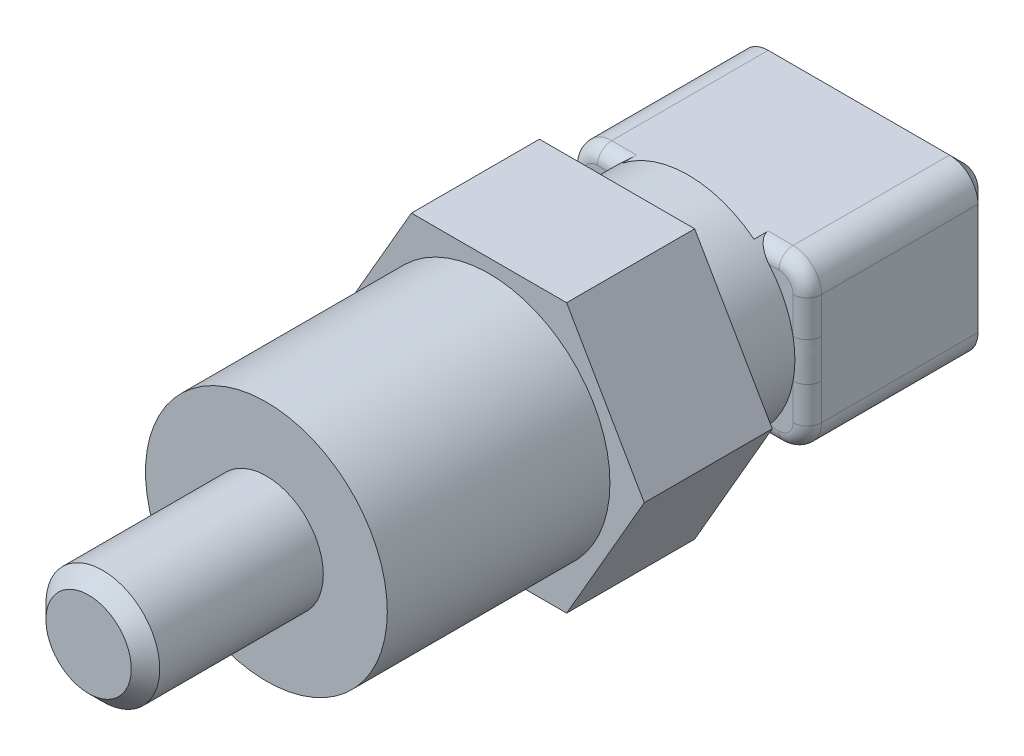
SolidWorks part; units mm, degrees
ref_plane "Front Plane" through (0, 0, 0) normal (0, 0, 1) x (1, 0, 0)
ref_plane "Top Plane" through (0, 0, 0) normal (0, 1, 0) x (1, 0, 0)
ref_plane "Right Plane" through (0, 0, 0) normal (1, 0, 0) x (0, 0, -1)
sketch "Sketch1" plane through (0, 0, 0) normal (0, 0, 1) x (1, 0, 0)
  line L0 (0, 23.3833) -> (0, -23.3833) construction
  line L1 (-5.456, 9.45) -> (-10.9119, 0)
  line L2 (-10.9119, 0) -> (-5.456, -9.45)
  line L3 (-5.456, -9.45) -> (5.456, -9.45)
  line L4 (5.456, -9.45) -> (10.9119, 0)
  line L5 (10.9119, 0) -> (5.456, 9.45)
  line L6 (5.456, 9.45) -> (-5.456, 9.45)
  circle A0 centre (0, 0) radius 9.45 construction
  dimension "D1" = 18.9
extrude "Extrude1" add sketch "Sketch1" along normal blind 9
sketch "Sketch2" plane through (0, 0, 9) normal (0, 0, 1) x (1, 0, 0)
  circle A0 centre (0, 0) radius 4.75
  dimension "D1" = 9.5
extrude "Extrude2" add sketch "Sketch2" along normal blind 3.15
chamfer "Chamfer1" distance 1 angle 45 1 edges at (4.75, 0, 9)
sketch "Sketch3" plane through (0, 0, 12.15) normal (0, 0, 1) x (1, 0, 0)
  circle A0 centre (0, 0) radius 8.5
  dimension "D1" = 17
extrude "Extrude3" add sketch "Sketch3" along normal blind 7.5
sketch "Sketch4" plane through (0, 0, 19.65) normal (0, 0, 1) x (1, 0, 0)
  circle A0 centre (0, 0) radius 4.2
  dimension "D1" = 8.4
extrude "Extrude4" add sketch "Sketch4" along normal blind 4
chamfer "Chamfer2" distance 0.5 angle 45 1 edges at (4.2, 0, 23.65)
sketch "Sketch5" plane through (0, 0, 23.65) normal (0, 0, 1) x (1, 0, 0)
  circle A0 centre (0, 0) radius 4
  dimension "D1" = 8
extrude "Extrude5" add sketch "Sketch5" along normal blind 13.5
chamfer "Chamfer3" distance 1 angle 45 1 edges at (4, 0, 37.15)
sketch "Sketch6" plane through (0, 0, 0) normal (0, 0, -1) x (-1, 0, 0)
  circle A0 centre (0, 0) radius 7.5
  dimension "D1" = 15
extrude "Extrude6" add sketch "Sketch6" along normal blind 5
sketch "Sketch7" plane through (0, 0, -5) normal (0, 0, -1) x (-1, 0, 0)
  line L0 (0, 11.8253) -> (0, -11.5236) construction
  line L1 (-6.375, 5.9) -> (6.375, 5.9)
  line L2 (-8.375, 3.9) -> (-8.375, -3.9)
  line L3 (-6.375, -5.9) -> (6.375, -5.9)
  line L4 (8.375, 3.9) -> (8.375, -3.9)
  line L5 (-16.9234, 0) -> (17.6229, 0) construction
  arc A0 (-8.375, 3.9) -> (-6.375, 5.9) centre (-6.375, 3.9) cw
  arc A1 (-6.375, -5.9) -> (-8.375, -3.9) centre (-6.375, -3.9) cw
  arc A2 (8.375, -3.9) -> (6.375, -5.9) centre (6.375, -3.9) cw
  arc A3 (6.375, 5.9) -> (8.375, 3.9) centre (6.375, 3.9) cw
  dimension "D3" = 2
  dimension "D1" = 11.8
  dimension "D2" = 16.75
extrude "Extrude7" add sketch "Sketch7" along normal blind 13
fillet "Fillet1" radius 1 10 edges at (-5.5027, -5.9, -5) (-7.7892, -5.3142, -5) (-5.5027, 5.9, -5) (-7.7892, 5.3142, -5) (5.5027, 5.9, -5) (7.7892, 5.3142, -5) (5.5027, -5.9, -5) (7.7892, -5.3142, -5) (-8.375, 0, -5) (8.375, 0, -5)
chamfer "Chamfer4" distance 1 angle 45 8 edges at (-7.7892, 5.3142, -18) (-8.375, 0, -18) (-7.7892, -5.3142, -18) (0, -5.9, -18) (7.7892, -5.3142, -18) (8.375, 0, -18) (7.7892, 5.3142, -18) (0, 5.9, -18)
sketch "Sketch8" plane through (0, 0, -18) normal (0, 0, -1) x (-1, 0, 0)
  line L12 (7.125, -3.9) -> (7.125, 3.9)
  line L13 (6.375, 4.65) -> (-6.375, 4.65)
  line L14 (-7.125, 3.9) -> (-7.125, -3.9)
  line L15 (-6.375, -4.65) -> (6.375, -4.65)
  line L16 (7.125, -3.9) -> (7.125, 3.9)
  line L17 (6.375, 4.65) -> (-6.375, 4.65)
  line L18 (-7.125, 3.9) -> (-7.125, -3.9)
  line L19 (-6.375, -4.65) -> (6.375, -4.65)
  arc A12 (7.125, 3.9) -> (6.375, 4.65) centre (6.375, 3.9) ccw
  arc A13 (-6.375, 4.65) -> (-7.125, 3.9) centre (-6.375, 3.9) ccw
  arc A14 (-7.125, -3.9) -> (-6.375, -4.65) centre (-6.375, -3.9) ccw
  arc A15 (6.375, -4.65) -> (7.125, -3.9) centre (6.375, -3.9) ccw
  arc A16 (7.125, 3.9) -> (6.375, 4.65) centre (6.375, 3.9) ccw
  arc A17 (-6.375, 4.65) -> (-7.125, 3.9) centre (-6.375, 3.9) ccw
  arc A18 (-7.125, -3.9) -> (-6.375, -4.65) centre (-6.375, -3.9) ccw
  arc A19 (6.375, -4.65) -> (7.125, -3.9) centre (6.375, -3.9) ccw
  dimension "D1" = 0.25
extrude "Cut-Extrude1" cut sketch "Sketch8" against normal blind 5
sketch "Sketch9" plane through (0, 0, 12.15) normal (0, 0, -1) x (-1, 0, 0)
  circle A1 centre (0, 0) radius 8.5
  circle A2 centre (0, 0) radius 8.5
  dimension "D1" = 0
extrude "Boss-Extrude1" add sketch "Sketch9" along normal up to surface (3.15 mm away) up to face at (5.75, 0, 9)
sketch "Sketch10" plane through (0, 0, 19.65) normal (0, 0, 1) x (1, 0, 0)
  circle A1 centre (0, 0) radius 8.5
  circle A2 centre (0, 0) radius 8.5
  dimension "D1" = 0
extrude "Boss-Extrude2" add sketch "Sketch10" along normal blind 5
